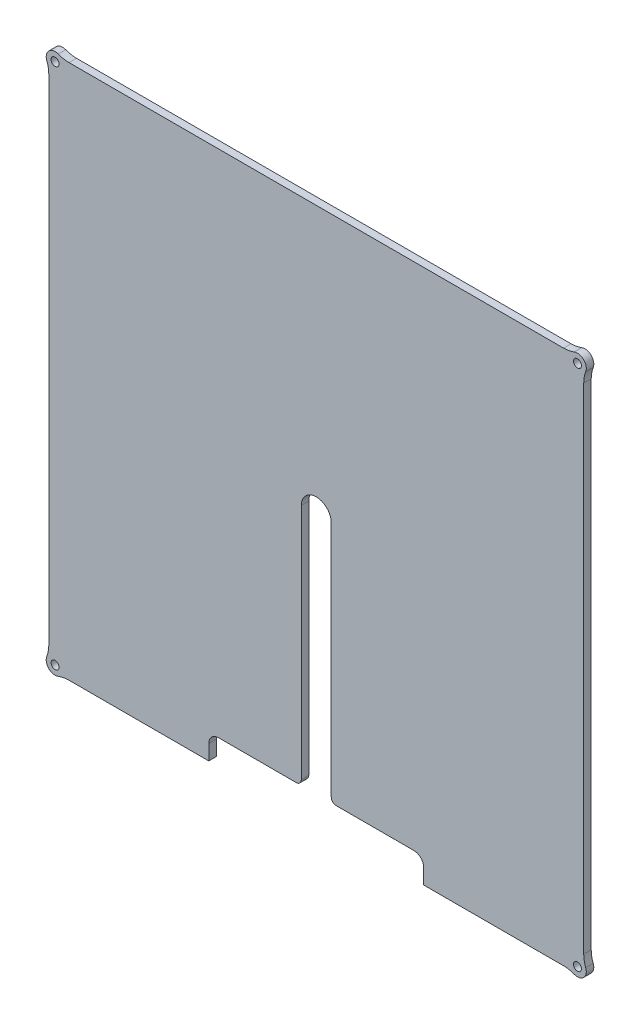
SolidWorks part; units mm, degrees
material "Balsa"
ref_plane "Front Plane" through (0, 0, 0) normal (0, 0, 1) x (1, 0, 0)
ref_plane "Top Plane" through (0, 0, 0) normal (0, 1, 0) x (1, 0, 0)
ref_plane "Right Plane" through (0, 0, 0) normal (1, 0, 0) x (0, 0, -1)
sketch "Sketch1" plane through (0, 0, 0) normal (0, 0, 1) x (1, 0, 0)
  line L0 (-107, 98.923) -> (-107, -98.923)
  line L1 (98.923, 107) -> (-98.923, 107)
  line L2 (107, -98.923) -> (107, 98.923)
  line L3 (43, -107) -> (98.923, -107)
  line L4 (43, -107) -> (43, -101)
  line L5 (39, -97) -> (-39, -97)
  line L6 (-43, -101) -> (-43, -107)
  line L7 (-98.923, -107) -> (-43, -107)
  line L9 (104.5, -104.5) -> (-104.5, -104.5) construction
  line L10 (104.5, -104.5) -> (104.5, 104.5) construction
  line L11 (104.5, 104.5) -> (-104.5, 104.5) construction
  line L12 (-104.5, -104.5) -> (-104.5, 104.5) construction
  line L13 (104.5, -104.5) -> (-104.5, 104.5) construction
  line L14 (104.5, 104.5) -> (-104.5, -104.5) construction
  circle A0 centre (-104.5, -104.5) radius 1.6
  circle A1 centre (-104.5, 104.5) radius 1.6
  circle A2 centre (104.5, 104.5) radius 1.6
  circle A3 centre (104.5, -104.5) radius 1.6
  arc A4 (43, -101) -> (39, -97) centre (39, -101) ccw
  arc A5 (-39, -97) -> (-43, -101) centre (-39, -101) ccw
  arc A6 (-103.2308, 107.7999) -> (-107.7999, 103.2308) centre (-104.5, 104.5) ccw
  arc A8 (-107.7999, -103.2308) -> (-103.2308, -107.7999) centre (-104.5, -104.5) ccw
  arc A9 (98.923, -107) -> (103.2308, -107.7999) centre (98.923, -119) cw
  arc A10 (103.2308, -107.7999) -> (107.7999, -103.2308) centre (104.5, -104.5) ccw
  arc A13 (107.7999, 103.2308) -> (103.2308, 107.7999) centre (104.5, 104.5) ccw
  arc A14 (107, -98.923) -> (107.7999, -103.2308) centre (119, -98.923) ccw
  arc A15 (-103.2308, -107.7999) -> (-98.923, -107) centre (-98.923, -119) cw
  arc A16 (-107, -98.923) -> (-107.7999, -103.2308) centre (-119, -98.923) cw
  arc A17 (-107.7999, 103.2308) -> (-107, 98.923) centre (-119, 98.923) cw
  arc A18 (-103.2308, 107.7999) -> (-98.923, 107) centre (-98.923, 119) ccw
  arc A19 (107, 98.923) -> (107.7999, 103.2308) centre (119, 98.923) cw
  arc A20 (103.2308, 107.7999) -> (98.923, 107) centre (98.923, 119) cw
  point P0 (0, 0)
  dimension "D1" = 12
  dimension "D3" = 12
  dimension "D4" = 12
  dimension "D5" = 12
  dimension "D6" = 12
  dimension "D7" = 12
  dimension "D2" = 209
  dimension "D8" = 214
  dimension "D9" = 10
extrude "Boss-Extrude1" add sketch "Sketch1" along normal blind 3
sketch "Sketch2" plane through (0, 0, 0) normal (0, 0, -1) x (-1, 0, 0)
  line L0 (39, -97) -> (-39, -97) construction
  line L1 (6, -97) -> (-6, -97)
  line L2 (6, -97) -> (6, 0)
  line L3 (6, 0) -> (-6, 0) construction
  line L4 (-6, -97) -> (-6, 0)
  line L5 (6, -97) -> (-6, 0) construction
  line L6 (6, 0) -> (-6, -97) construction
  arc A0 (6, 0) -> (-6, 0) centre (0, 0) ccw
  point P3 (0, -48.5)
  dimension "D1" = 6
extrude "Cut-Extrude1" cut sketch "Sketch2" against normal through all
fillet "Fillet1" radius 2 2 edges at (-6, -97, 1.5) (6, -97, 1.5)
